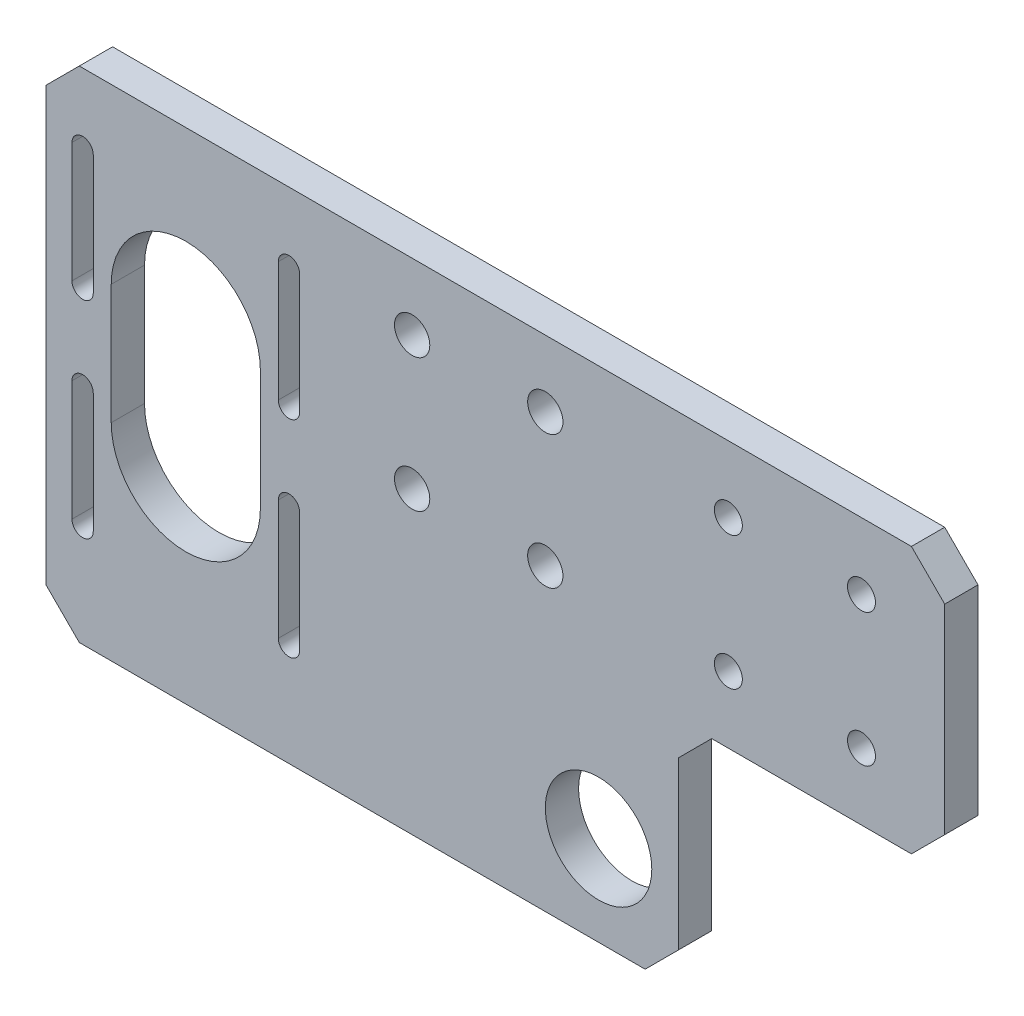
SolidWorks part; units mm, degrees
material "5052-O"
ref_plane "前基準面" through (0, 0, 0) normal (0, 0, 1) x (1, 0, 0)
ref_plane "上基準面" through (0, 0, 0) normal (0, 1, 0) x (1, 0, 0)
ref_plane "右基準面" through (0, 0, 0) normal (1, 0, 0) x (0, 0, -1)
sketch "草圖1" plane through (0, 0, 0) normal (0, 0, 1) x (1, 0, 0)
  line L1 (-47.5, -37.5) -> (47.5, -37.5)
  line L2 (-47.5, -37.5) -> (-47.5, 37.5)
  line L3 (-47.5, 37.5) -> (47.5, 37.5)
  line L4 (47.5, -37.5) -> (47.5, 37.5)
  line L5 (-47.5, -37.5) -> (47.5, 37.5) construction
  line L6 (-47.5, 37.5) -> (47.5, -37.5) construction
  point P0 (0, 0)
  dimension "D1" = 95
  dimension "D2" = 75
extrude "填料-伸長1" add sketch "草圖1" along normal blind 5
hole_wizard "M5 餘隙孔1" positions "草圖2" profile "草圖3" hole size "M5" standard "Ansi Metric" end condition through all
sketch "草圖2" plane through (0, 0, 5) normal (0, 0, 1) x (1, 0, 0)
  line L3 (7.5, 7.5) -> (27.5, 7.5) construction
  line L4 (7.5, 7.5) -> (7.5, 27.5) construction
  line L5 (7.5, 27.5) -> (27.5, 27.5) construction
  line L6 (27.5, 7.5) -> (27.5, 27.5) construction
  line L7 (7.5, 7.5) -> (27.5, 27.5) construction
  line L8 (7.5, 27.5) -> (27.5, 7.5) construction
  line L11 (47.5, 37.5) -> (-47.5, 37.5) construction
  line L12 (47.5, -37.5) -> (47.5, 37.5) construction
  point P6 (27.5, 27.5)
  point P15 (7.5, 7.5)
  point P16 (7.5, 27.5)
  point P17 (27.5, 7.5)
  point P35 (17.5, 17.5)
  dimension "D1" = 20
  dimension "D2" = 20
  dimension "D3" = 20
  dimension "D4" = 20
sketch "草圖3" plane through (27.5, 27.5, 5) normal (1, 0, 0) x (0, -1, 0)
  line L0 (0, 0) -> (0, 5)
  line L1 (0, 5) -> (2.65, 5)
  line L2 (2.65, 5) -> (2.65, 0)
  line L5 (2.65, 0) -> (0, 0)
  line L11 (0, -6.35) -> (0, 107.95) construction
  dimension "貫穿孔直徑" = 5.3
  dimension "貫穿孔深度" = 5
sketch "草圖6" plane through (0, 0, 5) normal (0, 0, 1) x (1, 0, 0)
  line L0 (47.5, 37.5) -> (-47.5, 37.5) construction
  line L2 (-26.5, -6.5) -> (-26.5, 11.5) construction
  line L3 (-37.7, -6.5) -> (-37.7, 11.5)
  line L4 (-15.3, -6.5) -> (-15.3, 11.5)
  line L6 (-42, 27) -> (-42, 9) construction
  line L7 (-42, -4) -> (-11, -4) construction
  line L8 (-42, -4) -> (-42, 27) construction
  line L9 (-42, 27) -> (-11, 27) construction
  line L10 (-11, -4) -> (-11, 27) construction
  line L11 (-42, -4) -> (-11, 27) construction
  line L12 (-42, 27) -> (-11, -4) construction
  line L13 (-40.4, 27) -> (-40.4, 9)
  line L14 (-43.6, 27) -> (-43.6, 9)
  line L15 (-11, 27) -> (-11, 9) construction
  line L16 (-9.4, 27) -> (-9.4, 9)
  line L17 (-12.6, 27) -> (-12.6, 9)
  line L18 (-11, -4) -> (-11, -22) construction
  line L19 (-9.4, -4) -> (-9.4, -22)
  line L20 (-12.6, -4) -> (-12.6, -22)
  line L21 (-42, -4) -> (-42, -22) construction
  line L22 (-40.4, -4) -> (-40.4, -22)
  line L23 (-43.6, -4) -> (-43.6, -22)
  line L25 (-47.5, 37.5) -> (-47.5, -37.5) construction
  arc A0 (-37.7, -6.5) -> (-15.3, -6.5) centre (-26.5, -6.5) ccw
  arc A1 (-15.3, 11.5) -> (-37.7, 11.5) centre (-26.5, 11.5) ccw
  arc A2 (-40.4, 27) -> (-43.6, 27) centre (-42, 27) ccw
  arc A3 (-43.6, 9) -> (-40.4, 9) centre (-42, 9) ccw
  arc A4 (-9.4, 27) -> (-12.6, 27) centre (-11, 27) ccw
  arc A5 (-12.6, 9) -> (-9.4, 9) centre (-11, 9) ccw
  arc A6 (-9.4, -4) -> (-12.6, -4) centre (-11, -4) ccw
  arc A7 (-12.6, -22) -> (-9.4, -22) centre (-11, -22) ccw
  arc A8 (-40.4, -4) -> (-43.6, -4) centre (-42, -4) ccw
  arc A9 (-43.6, -22) -> (-40.4, -22) centre (-42, -22) ccw
  point P6 (-26.5, 2.5)
  point P13 (-26.5, 11.5)
  point P18 (-42, 18)
  point P24 (-11, 18)
  point P30 (-11, -13)
  point P36 (-42, -13)
  dimension "D3" = 11.2
  dimension "D7" = 1.6
  dimension "D1" = 18
  dimension "D2" = 21
  dimension "D4" = 35
  dimension "D5" = 31
  dimension "D6" = 31
extrude "除料-伸長2" cut sketch "草圖6" against normal through all
sketch "草圖4" plane through (0, 0, 5) normal (0, 0, 1) x (1, 0, 0)
  circle A0 centre (35.5, -24) radius 8
  circle A1 centre (27.5, 7.5) radius 2.65 construction
  point P7 (0, 0)
  point P8 (0, 0)
  dimension "D3" = 16
  dimension "D1" = 31.5
  dimension "D2" = 8
sketch "Sketch1" plane through (47.5, 0, 0) normal (1, 0, 0) x (0, 0, -1)
  line L0 (0, -37.5) -> (0, 37.5) construction
  line L1 (-5, 37.5) -> (0, 37.5)
  line L2 (-5, 37.5) -> (-5, -2.5)
  line L3 (-5, -2.5) -> (0, -2.5)
  line L4 (0, 37.5) -> (0, -2.5)
  dimension "D1" = 40
extrude "Boss-Extrude1" add sketch "Sketch1" along normal blind 40
hole_wizard "Ø4.2 (4.2) Diameter Hole1" positions "Sketch4" profile "Sketch5" hole size "Ø4.2" standard "ANSI Metric" end condition up to next
sketch "Sketch4" plane through (0, 0, 5) normal (0, 0, 1) x (1, 0, 0)
  line L1 (75, 27.5) -> (55, 27.5) construction
  line L2 (75, 27.5) -> (75, 7.5) construction
  line L3 (75, 7.5) -> (55, 7.5) construction
  line L4 (55, 27.5) -> (55, 7.5) construction
  line L5 (87.5, 37.5) -> (87.5, -2.5) construction
  line L6 (87.5, 37.5) -> (-47.5, 37.5) construction
  point P0 (75, 27.5)
  point P2 (75, 7.5)
  point P4 (55, 27.5)
  point P6 (55, 7.5)
  dimension "D1" = 20
  dimension "D2" = 20
  dimension "D3" = 12.5
  dimension "D4" = 10
sketch "Sketch5" plane through (75, 27.5, 5) normal (1, 0, 0) x (0, -1, 0)
  line L0 (0, 0) -> (0, 5)
  line L1 (0, 5) -> (2.1, 5)
  line L2 (2.1, 5) -> (2.1, 0)
  line L5 (2.1, 0) -> (0, 0)
  line L11 (0, -6.35) -> (0, 107.95) construction
  dimension "Thru Hole Dia." = 4.2
  dimension "Thru Hole Depth" = 5
extrude "除料-伸長3" cut sketch "草圖4" against normal up to next
chamfer "導角4" distance 5 angle 45 6 edges at (-47.5, 37.5, 2.5) (-47.5, -37.5, 2.5) (47.5, -37.5, 2.5) (47.5, -2.5, 2.5) (87.5, -2.5, 2.5) (87.5, 37.5, 2.5)
